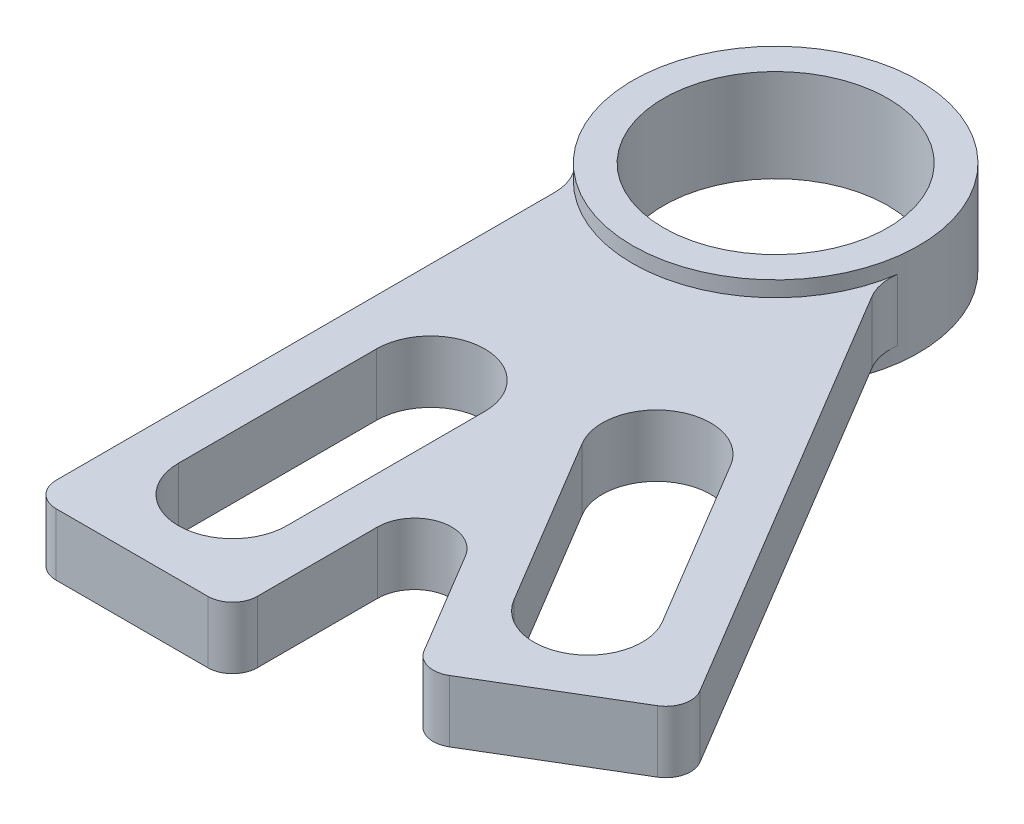
SolidWorks part; units mm, degrees
material "AISI 4130 Steel, normalized at 870C"
ref_plane "Front Plane" through (0, 0, 0) normal (0, 0, 1) x (1, 0, 0)
ref_plane "Top Plane" through (0, 0, 0) normal (0, 1, 0) x (1, 0, 0)
ref_plane "Right Plane" through (0, 0, 0) normal (1, 0, 0) x (0, 0, -1)
sketch "Sketch1" plane through (0, 0, 0) normal (0, 1, 0) x (1, 0, 0)
  line L0 (0, 0) -> (0, -66.04) construction
  line L1 (0, 0) -> (33.8815, -56.6862) construction
  line L2 (0, -55.7213) -> (0, -35.4013) construction
  line L3 (-5.5562, -55.7213) -> (-5.5562, -35.4013)
  line L4 (5.5563, -55.7213) -> (5.5563, -35.4013)
  line L5 (28.5875, -47.829) -> (18.1624, -30.3871) construction
  line L6 (23.8182, -50.6796) -> (13.3931, -33.2377)
  line L7 (33.3568, -44.9784) -> (22.9317, -27.5365)
  line L8 (0, -66.04) -> (0, -61.2775) construction
  line L9 (33.8815, -56.6862) -> (31.4381, -52.5983) construction
  line L10 (-10.3187, -66.04) -> (10.3188, -66.04)
  line L11 (25.0242, -61.9802) -> (42.7387, -51.3923)
  line L12 (-10.3187, -66.04) -> (-10.3187, -10.4432)
  line L13 (10.3188, -66.04) -> (10.3188, -37.3768)
  line L14 (42.7387, -51.3923) -> (14.2151, -3.6701)
  line L15 (25.0242, -61.9802) -> (10.3188, -37.3768)
  line L16 (188.8389, -315.9417) -> (17.7009, -29.6149) construction
  line L22 (0, 0) -> (10.3188, -37.3768) construction
  circle A0 centre (0, 0) radius 11.5062
  circle A1 centre (0, 0) radius 14.6812
  arc A2 (-5.5562, -55.7213) -> (5.5563, -55.7213) centre (0, -55.7213) ccw
  arc A3 (5.5563, -35.4013) -> (-5.5562, -35.4013) centre (0, -35.4013) ccw
  arc A4 (23.8182, -50.6796) -> (33.3568, -44.9784) centre (28.5875, -47.829) ccw
  arc A5 (22.9317, -27.5365) -> (13.3931, -33.2377) centre (18.1624, -30.3871) ccw
  point P8 (0, -45.5613)
  point P13 (23.3749, -39.108)
  point P25 (0, -66.04)
  point P27 (33.8815, -56.6862)
  dimension "D2" = 29.3624
  dimension "D3" = 4.7625
  dimension "D4" = 4.7625
  dimension "D5" = 20.32
  dimension "D6" = 66.04
  dimension "D7" = 20.6375
extrude "Bearing_Insert_Extrude" add sketch "Sketch1" along normal mid plane 9.525 contours A1 A0 region at (-5.4988, 0, -13.1636)
extrude "Apex_Slot_Insert_Extrude" add sketch "Sketch1<4>" along normal mid plane 6.35 contours A1 L12 L10 L13 L15 L11 L14 A5 L7 A4 L6 A3 L4 A2 L3 | L13 L15 region at (9.9891, 0, 36.1827)
sketch "Sketch1<4>" plane through (0, 0, 0) normal (0, 1, 0) x (1, 0, 0) same geometry as "Sketch1"
fillet "Fillet1" radius 5.08 2 edges at (14.2151, 0, 3.6701) (-10.3187, 0, 10.4432)
fillet "Fillet2" radius 2.54 4 edges at (42.7387, 0, 51.3923) (25.0242, 0, 61.9802) (10.3188, 0, 66.04) (-10.3187, 0, 66.04)
fillet "Fillet3" radius 3.81 1 edges at (10.3188, 0, 37.3768)
equation "\"Apex_thickness\"= .25"
equation "\"Bearing_diameter\"= 0.906in"
equation "\"A-arm_angle\"= 39.1893"
equation "\"D1@Sketch1\"=\"Bearing_diameter\""
equation "\"D1@Apex_Slot_Insert_Extrude\"=\"Apex_thickness\""
